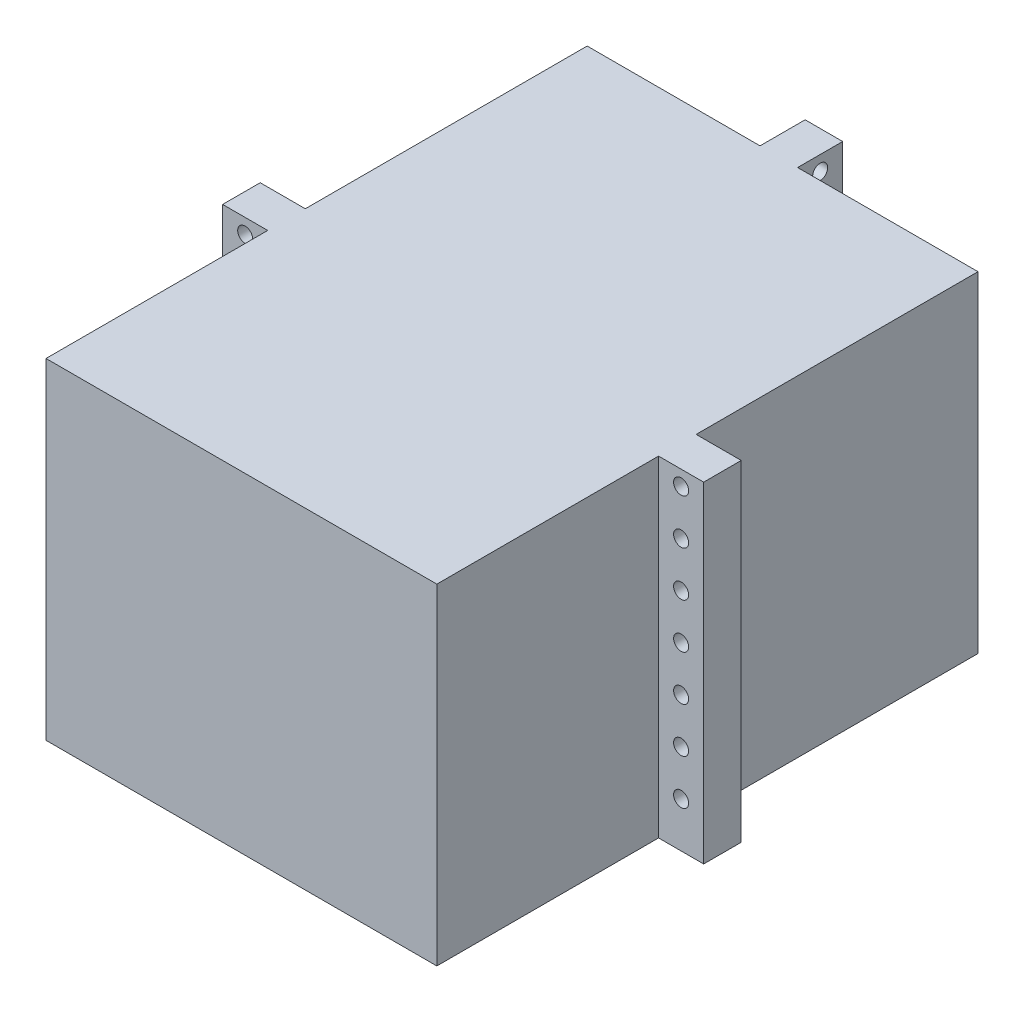
SolidWorks part; units mm, degrees
material "6061 Alloy"
ref_plane "Front Plane" through (0, 0, 0) normal (0, 0, 1) x (1, 0, 0)
ref_plane "Top Plane" through (0, 0, 0) normal (0, 1, 0) x (1, 0, 0)
ref_plane "Right Plane" through (0, 0, 0) normal (1, 0, 0) x (0, 0, -1)
sketch "Sketch1" plane through (0, 0, 0) normal (0, 1, 0) x (1, 0, 0)
  line L0 (-19.05, -228.6) -> (19.05, -228.6) construction
  line L1 (165.1, 228.6) -> (-165.1, 228.6) construction
  line L2 (165.1, 228.6) -> (165.1, -228.6) construction
  line L3 (165.1, -228.6) -> (-165.1, -228.6) construction
  line L4 (-165.1, 228.6) -> (-165.1, -228.6) construction
  line L5 (165.1, 228.6) -> (-165.1, -228.6) construction
  line L6 (165.1, -228.6) -> (-165.1, 228.6) construction
  line L7 (-19.05, -228.6) -> (-19.05, -269.875) construction
  line L8 (19.05, -228.6) -> (19.05, -269.875) construction
  line L9 (-19.05, -269.875) -> (19.05, -269.875) construction
  line L10 (-165.1, -228.6) -> (-19.05, -228.6)
  line L11 (19.05, -228.6) -> (-19.05, -228.6)
  line L12 (12.7, 228.6) -> (-19.05, 228.6) construction
  line L13 (12.7, 228.6) -> (12.7, 266.7)
  line L14 (19.05, -228.6) -> (165.1, -228.6)
  line L15 (-19.05, 228.6) -> (-19.05, 266.7)
  line L16 (12.7, 266.7) -> (-19.05, 266.7)
  line L17 (-19.05, 228.6) -> (-165.1, 228.6)
  line L18 (12.7, 228.6) -> (165.1, 228.6)
  line L19 (-165.1, -9.525) -> (-203.2, -9.525)
  line L20 (-165.1, -9.525) -> (-165.1, -41.275) construction
  line L21 (-203.2, -9.525) -> (-203.2, -41.275)
  line L22 (-165.1, -41.275) -> (-203.2, -41.275)
  line L23 (165.1, -9.525) -> (165.1, -41.275) construction
  line L24 (165.1, -9.525) -> (203.2, -9.525)
  line L25 (165.1, -41.275) -> (203.2, -41.275)
  line L26 (203.2, -9.525) -> (203.2, -41.275)
  line L27 (-165.1, 228.6) -> (-165.1, -9.525)
  line L28 (-165.1, -41.275) -> (-165.1, -228.6)
  line L29 (165.1, -41.275) -> (165.1, -228.6)
  line L30 (165.1, -9.525) -> (165.1, 228.6)
  point P0 (0, 0)
  point P6 (184.15, -9.525)
  point P13 (-3.175, 228.6)
  point P22 (184.15, -41.275)
  point P25 (-184.15, -41.275)
  dimension "D1" = 330.2
  dimension "D2" = 457.2
  dimension "D3" = 146.05
  dimension "D4" = 146.05
  dimension "D5" = 41.275
  dimension "D6" = 146.05
  dimension "D7" = 31.75
  dimension "D8" = 38.1
  dimension "D9" = 238.125
  dimension "D10" = 238.125
  dimension "D11" = 31.75
  dimension "D12" = 31.75
  dimension "D13" = 38.1
  dimension "D14" = 38.1
extrude "Boss-Extrude1" add sketch "Sketch1" along normal blind 279.4
ref_point "Point2"
ref_axis "Axis1" through (0, 139.7, 228.6) along (0, 1, 0)
sketch "Sketch2" plane through (0, 0, 41.275) normal (0, 0, 1) x (1, 0, 0)
  line L0 (-184.15, 279.4) -> (-184.15, 0) construction
  line L1 (-203.2, 279.4) -> (-165.1, 279.4) construction
  line L2 (-203.2, 0) -> (-165.1, 0) construction
  line L3 (-165.1, 279.4) -> (-165.1, 0) construction
  line L4 (0, 135.6782) -> (0, 345.0284)
  line L5 (0, 139.7) -> (0, 351.1275) construction
  line L6 (184.15, 279.4) -> (184.15, 0) construction
  circle A0 centre (-184.15, 38.1) radius 6.35
  circle A1 centre (-184.15, 76.2) radius 6.35
  circle A2 centre (-184.15, 114.3) radius 6.35
  circle A3 centre (-184.15, 152.4) radius 6.35
  circle A4 centre (-184.15, 190.5) radius 6.35
  circle A5 centre (-184.15, 228.6) radius 6.35
  circle A6 centre (-184.15, 266.7) radius 6.35
  circle A7 centre (184.15, 266.7) radius 6.35
  circle A8 centre (184.15, 228.6) radius 6.35
  circle A9 centre (184.15, 190.5) radius 6.35
  circle A10 centre (184.15, 152.4) radius 6.35
  circle A11 centre (184.15, 114.3) radius 6.35
  circle A12 centre (184.15, 76.2) radius 6.35
  circle A13 centre (184.15, 38.1) radius 6.35
  point P10 (-184.15, 53.7554)
  point P25 (0, 0)
  point P26 (0, 0)
  point P45 (184.15, 53.7554)
  dimension "D2" = 12.7
  dimension "D1" = 19.05
  dimension "D3" = 38.1
  dimension "D4" = 7
extrude "Cut-Extrude1" cut sketch "Sketch2" against normal blind 45.72 contours A6 | A5 | A3 | A4 | A2 | A1 | A0 | A7 | A8 | A9 | A10 | A11 | A12 | A13
sketch "Sketch3" plane through (-19.05, 0, 0) normal (-1, 0, 0) x (0, 0, 1)
  line L0 (-247.65, 279.4) -> (-247.65, 0) construction
  line L1 (-266.7, 279.4) -> (-228.6, 279.4) construction
  line L2 (-266.7, 0) -> (-228.6, 0) construction
  line L3 (-228.6, 279.4) -> (-228.6, 0) construction
  circle A0 centre (-247.65, 38.1) radius 6.35
  circle A1 centre (-247.65, 76.2) radius 6.35
  circle A2 centre (-247.65, 114.3) radius 6.35
  circle A3 centre (-247.65, 152.4) radius 6.35
  circle A4 centre (-247.65, 190.5) radius 6.35
  circle A5 centre (-247.65, 228.6) radius 6.35
  circle A6 centre (-247.65, 266.7) radius 6.35
  point P10 (-247.65, 53.0999)
  dimension "D2" = 12.7
  dimension "D1" = 19.05
  dimension "D3" = 38.1
  dimension "D4" = 7
extrude "Cut-Extrude2" cut sketch "Sketch3" against normal blind 45.72
